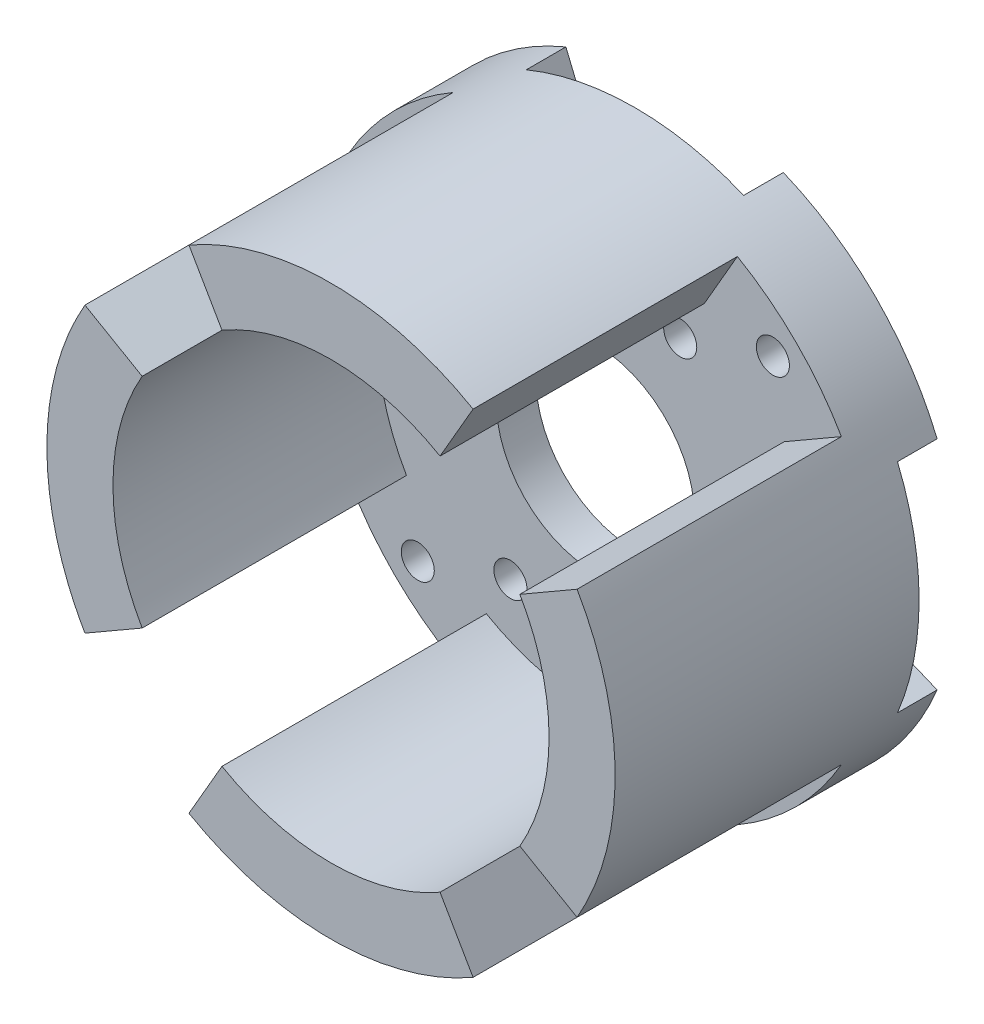
SolidWorks part; units mm, degrees
ref_plane "Front Plane" through (0, 0, 0) normal (0, 0, 1) x (1, 0, 0)
ref_plane "Top Plane" through (0, 0, 0) normal (0, 1, 0) x (1, 0, 0)
ref_plane "Right Plane" through (0, 0, 0) normal (1, 0, 0) x (0, 0, -1)
sketch "Sketch1" plane through (0, 0, 0) normal (0, 0, 1) x (1, 0, 0)
  line L0 (-19, 0) -> (-21.5, 0) construction
  line L1 (-13.435, 13.435) -> (13.435, -13.435) construction
  line L2 (-13.435, -13.435) -> (13.435, 13.435) construction
  line L3 (-13.435, 13.435) -> (13.435, 13.435) construction
  line L4 (0, 0) -> (-8.2277, 19.8634) construction
  line L5 (0, 0) -> (8.2277, 19.8634) construction
  line L6 (0, 0) -> (0, 21.5) construction
  line L7 (-6.3143, 15.244) -> (-8.2277, 19.8634)
  line L8 (6.3143, 15.244) -> (8.2277, 19.8634)
  line L9 (-15.244, -6.3143) -> (-19.8634, -8.2277)
  line L10 (-15.244, 6.3143) -> (-19.8634, 8.2277)
  line L11 (-6.3143, -15.244) -> (-8.2277, -19.8634)
  line L12 (6.3143, -15.244) -> (8.2277, -19.8634)
  line L13 (15.244, 6.3143) -> (19.8634, 8.2277)
  line L14 (15.244, -6.3143) -> (19.8634, -8.2277)
  line L15 (0, 16.5) -> (0, 11.5)
  line L17 (-12.85, 0) -> (-6.425, -11.1284) construction
  line L18 (-6.425, -11.1284) -> (6.425, -11.1284) construction
  line L19 (6.425, -11.1284) -> (12.85, 0) construction
  line L20 (12.85, 0) -> (6.425, 11.1284) construction
  line L21 (6.425, 11.1284) -> (-6.425, 11.1284) construction
  line L22 (-6.425, 11.1284) -> (-12.85, 0) construction
  circle A0 centre (0, 0) radius 21.5
  circle A1 centre (0, 0) radius 19 construction
  circle A2 centre (-13.435, 13.435) radius 1.25
  circle A3 centre (13.435, 13.435) radius 1.25
  circle A4 centre (13.435, -13.435) radius 1.25
  circle A5 centre (-13.435, -13.435) radius 1.25
  arc A6 (-6.3143, 15.244) -> (6.3143, 15.244) centre (0, 0) cw
  arc A7 (-15.244, 6.3143) -> (-15.244, -6.3143) centre (0, 0) ccw
  arc A8 (6.3143, -15.244) -> (-6.3143, -15.244) centre (0, 0) cw
  arc A9 (15.244, -6.3143) -> (15.244, 6.3143) centre (0, 0) ccw
  circle A11 centre (0, 0) radius 11 construction
  circle A12 centre (0, 0) radius 12.85 construction
  circle A13 centre (0, 0) radius 11.1284 construction
  circle A14 centre (-12.85, 0) radius 1.25
  circle A15 centre (-6.425, 11.1284) radius 1.25
  circle A16 centre (6.425, 11.1284) radius 1.25
  circle A17 centre (12.85, 0) radius 1.25
  circle A18 centre (6.425, -11.1284) radius 1.25
  circle A19 centre (-6.425, -11.1284) radius 1.25
  circle A20 centre (0, 0) radius 7.5
  circle A21 centre (0, 0) radius 16.5
  point P16 (0, 13.435)
  point P20 (0, 16.5)
  dimension "D1" = 43
  dimension "D3" = 2.5
  dimension "D7" = 22
  dimension "D8" = 25.7
  dimension "D9" = 2.5
  dimension "D10" = 15
  dimension "D2" = 2.5
  dimension "D4" = 5
  dimension "D5" = 45
  dimension "D6" = 5
extrude "Boss-Extrude1" add sketch "Sketch1" along normal blind 3 contours A21 L7 A0 L10 A2 | L7 A6 L8 A0 | A21 L13 A0 L8 A3 | A9 L14 A0 L13 | A21 L12 A0 L14 A4 | L12 A8 L11 A0 | A21 L9 A0 L11 A5 | A7 L10 A0 L9 | A9 A21 A6 A7 A8 A20 A19 A18 A17 A16 A15 A14 region at (-11.8028, 11.8028, 0) region at (0, 18.6223, 0) region at (-3.1279, 15.7252, 0) region at (-18.6223, 0, 0) region at (15.0673, 15.0673, 0) region at (-11.8028, -11.8028, 0) region at (18.6223, 0, 0) region at (0, -18.6223, 0) region at (11.8028, -11.8028, 0)
extrude "Boss-Extrude2" add sketch "Sketch1<3>" against normal blind 3 contours A11 | A21 L7 A0 L10 A2 | A21 L13 A0 L8 A3 | A21 L12 A0 L14 A4 | A21 L9 A0 L11 A5 region at (-11.8028, 11.8028, 0) region at (15.0673, 15.0673, 0) region at (-11.8028, -11.8028, 0) region at (11.8028, -11.8028, 0)
sketch "Sketch1<3>" plane through (0, 0, 0) normal (0, 0, 1) x (1, 0, 0) same geometry as "Sketch1"
sketch "Sketch7" plane through (0, 0, 3) normal (0, 0, 1) x (1, 0, 0)
  line L0 (0, 0) -> (-21.5, 0) construction
  line L1 (0, 0) -> (-18.6195, 10.75) construction
  line L2 (0, 0) -> (-18.6195, -10.75) construction
  line L3 (-14.2894, 8.25) -> (-18.6195, 10.75)
  line L4 (-14.2894, -8.25) -> (-18.6195, -10.75)
  line L5 (8.25, 14.2894) -> (10.75, 18.6195)
  line L6 (-8.25, 14.2894) -> (-10.75, 18.6195)
  line L7 (14.2894, -8.25) -> (18.6195, -10.75)
  line L8 (14.2894, 8.25) -> (18.6195, 10.75)
  line L9 (-8.25, -14.2894) -> (-10.75, -18.6195)
  line L10 (8.25, -14.2894) -> (10.75, -18.6195)
  line L11 (0, 0) -> (-14.2894, 8.25) construction
  circle A0 centre (0, 0) radius 16.5 construction
  circle A1 centre (0, 0) radius 21.5 construction
  circle A2 centre (0, 0) radius 21.5
  arc A3 (-14.2894, 8.25) -> (-14.2894, -8.25) centre (0, 0) ccw
  arc A4 (8.25, 14.2894) -> (-8.25, 14.2894) centre (0, 0) ccw
  arc A5 (14.2894, -8.25) -> (14.2894, 8.25) centre (0, 0) ccw
  arc A6 (-8.25, -14.2894) -> (8.25, -14.2894) centre (0, 0) ccw
  point P8 (9.0061, 13.8253)
  point P10 (-16.5, 0)
  point P11 (0, 16.5)
  circle M18 centre (0, 0) radius 21.5
  dimension "D1" = 33
  dimension "D2" = 60
  dimension "D3" = 4
extrude "Boss-Extrude6" add sketch "Sketch7" along normal blind 20 contours A4 L5 L6 M18 | A5 L7 L8 M18 | A6 L9 L10 M18 | A3 L3 L4 M18 region at (-18.2484, 0, 3) region at (0, 18.2484, 3) region at (0, -18.2484, 3) region at (18.2484, 0, 3)
